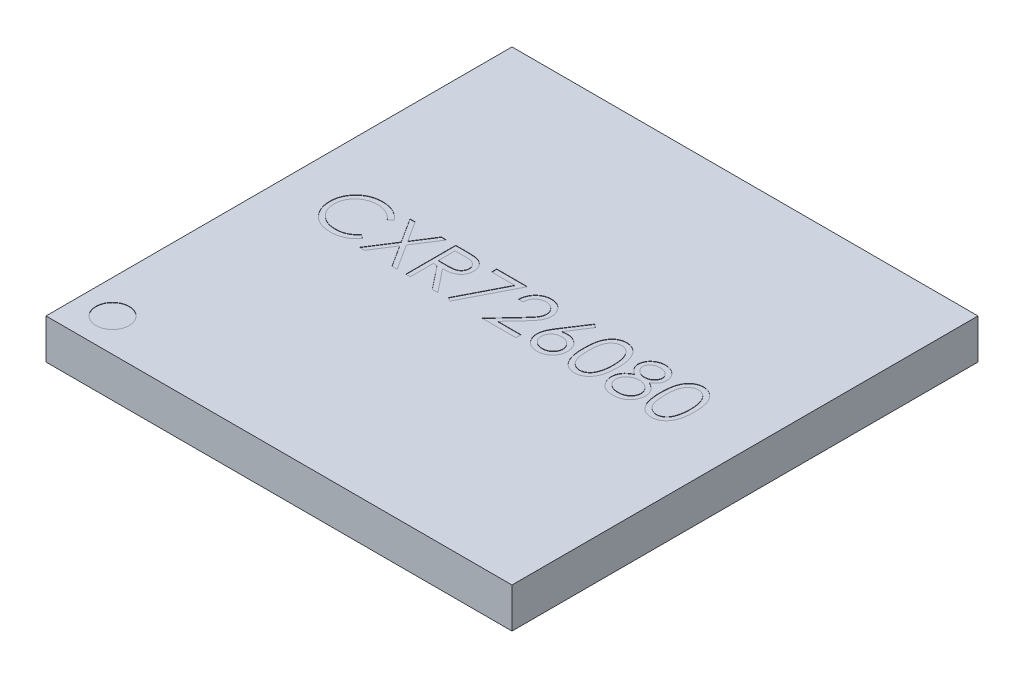
SolidWorks part; units mm, degrees
ref_plane "Ebene vorne" through (0, 0, 0) normal (0, 0, 1) x (1, 0, 0)
ref_plane "Ebene oben" through (0, 0, 0) normal (0, 1, 0) x (1, 0, 0)
ref_plane "Ebene rechts" through (0, 0, 0) normal (1, 0, 0) x (0, 0, -1)
sketch "Skizze1" plane through (0, 0, 0) normal (0, 1, 0) x (1, 0, 0)
  line L1 (-7, -7) -> (7, -7)
  line L2 (-7, -7) -> (-7, 7)
  line L3 (-7, 7) -> (7, 7)
  line L4 (7, -7) -> (7, 7)
  line L5 (-7, -7) -> (7, 7) construction
  line L6 (-7, 7) -> (7, -7) construction
  point P0 (0, 0)
  dimension "D1" = 14
extrude "Aufsatz-Linear austragen1" add sketch "Skizze1" along normal blind 1.2
sketch "Skizze2" plane through (0, 1.2, 0) normal (0, 1, 0) x (1, 0, 0)
  circle A0 centre (-6, -6) radius 0.5
  text T0 "CXR726080" font "Century Gothic" height 1.5
  dimension "D1" = 1
  dimension "D2" = 6
  dimension "D3" = 6
extrude "Schnitt-Linear austragen1" cut sketch "Skizze2" against normal blind 0.01
sketch "Skizze3" plane through (0, 0, 0) normal (0, -1, 0) x (1, 0, 0)
  circle A0 centre (-6, 6) radius 0.25
  dimension "D1" = 0.5
  dimension "D2" = 6
  dimension "D3" = 6
extrude "Aufsatz-Linear austragen2" add sketch "Skizze3" along normal blind 0.35
fillet "Verrundung1" radius 0.25 1 edges at (-6, -0.35, 5.75)
pattern_linear "Lineares Muster1" count 13 spacing 1 along (1, 0, 0) count 13 spacing 1 along (0, 0, -1) of "Aufsatz-Linear austragen2", "Verrundung1"
sketch "Skizze4" plane through (0, 0, 0) normal (0, 1, 0) x (1, 0, 0)
  line L1 (-6.4758, -6.4825) -> (-5.5904, -6.4825)
  line L2 (-6.4758, -6.4825) -> (-6.4758, -5.6631)
  line L3 (-6.4758, -5.6631) -> (-5.5904, -5.6631)
  line L4 (-5.5904, -6.4825) -> (-5.5904, -5.6631)
  line L5 (5.5772, -6.4825) -> (6.3569, -6.4825)
  line L6 (5.5772, -6.4825) -> (5.5772, -5.6631)
  line L7 (5.5772, -5.6631) -> (6.3569, -5.6631)
  line L8 (6.3569, -6.4825) -> (6.3569, -5.6631)
  line L9 (-6.3437, 5.6234) -> (-5.5904, 5.6234)
  line L10 (-6.3437, 5.6234) -> (-6.3437, 6.456)
  line L11 (-6.3437, 6.456) -> (-5.5904, 6.456)
  line L12 (-5.5904, 5.6234) -> (-5.5904, 6.456)
  line L13 (5.5772, 5.6234) -> (6.4626, 5.6234)
  line L14 (5.5772, 5.6234) -> (5.5772, 6.456)
  line L15 (5.5772, 6.456) -> (6.4626, 6.456)
  line L16 (6.4626, 5.6234) -> (6.4626, 6.456)
  line L17 (-0.4758, -0.4163) -> (0.4493, -0.4163)
  line L18 (-0.4758, -0.4163) -> (-0.4758, 0.4692)
  line L19 (-0.4758, 0.4692) -> (0.4493, 0.4692)
  line L20 (0.4493, -0.4163) -> (0.4493, 0.4692)
extrude "Schnitt-Linear austragen2" cut sketch "Skizze4" against normal through all
